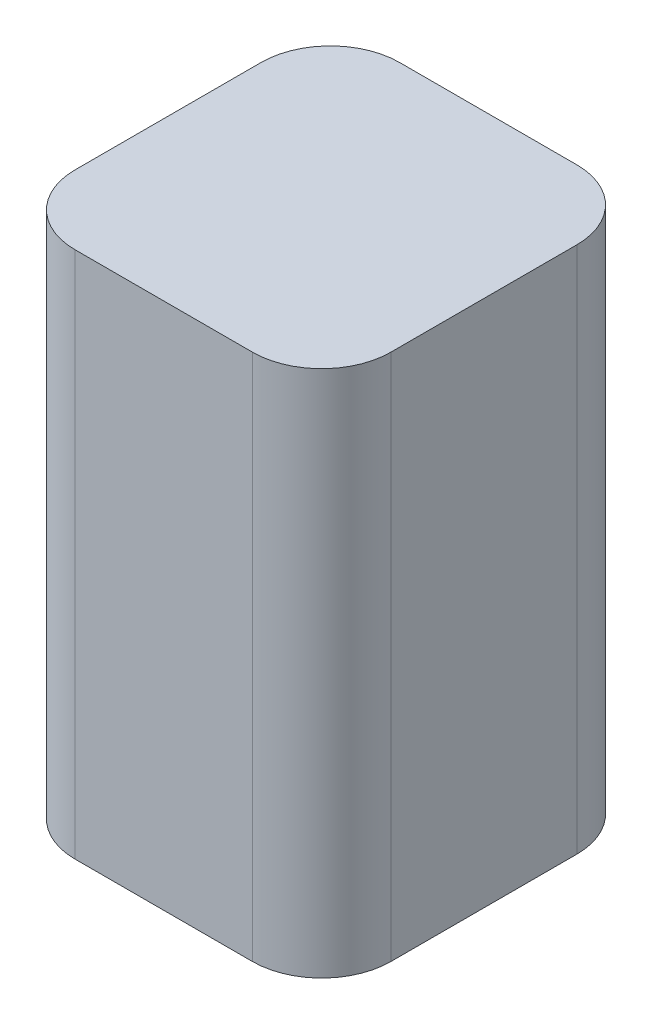
SolidWorks part; units mm, degrees
material "1060 Alloy"
ref_plane "Front Plane" through (0, 0, 0) normal (0, 0, 1) x (1, 0, 0)
ref_plane "Top Plane" through (0, 0, 0) normal (0, 1, 0) x (1, 0, 0)
ref_plane "Right Plane" through (0, 0, 0) normal (1, 0, 0) x (0, 0, -1)
sketch "Sketch1" plane through (0, 0, 0) normal (0, 0, 1) x (1, 0, 0)
  line L1 (-4.6355, 7.747) -> (4.6355, 7.747)
  line L2 (-4.6355, 7.747) -> (-4.6355, -7.747)
  line L3 (-4.6355, -7.747) -> (4.6355, -7.747)
  line L4 (4.6355, 7.747) -> (4.6355, -7.747)
  line L5 (-4.6355, 7.747) -> (4.6355, -7.747) construction
  line L6 (-4.6355, -7.747) -> (4.6355, 7.747) construction
  point P0 (0, 0)
  dimension "D1" = 9.271
  dimension "D2" = 15.494
extrude "Boss-Extrude1" add sketch "Sketch1" against normal blind 9.525
hole_wizard "1/4 (0.25) Diameter Hole1" positions "Sketch3" profile "Sketch2" hole size "1/4" standard "Ansi Inch"
sketch "Sketch3" plane through (0, 0, -9.525) normal (0, 0, -1) x (-1, 0, 0)
  point P0 (0, 0)
sketch "Sketch2" plane through (0, 0, -9.525) normal (1, 0, 0) x (0, 1, 0)
  line L0 (0, 0) -> (0, 8.2577)
  line L1 (0, 8.2577) -> (3.175, 6.35)
  line L2 (3.175, 6.35) -> (3.175, 0)
  line L5 (3.175, 0) -> (0, 0)
  line L10 (0, 8.2577) -> (-3.175, 6.35) construction
  line L11 (0, -6.35) -> (0, 107.95) construction
  dimension "Hole Dia." = 6.35
  dimension "Hole Depth" = 6.35
  dimension "Drill Angle" = 118
fillet "Fillet1" radius 2.032 4 edges at (-4.6355, 0, 0) (4.6355, 0, 0) (-4.6355, 0, -9.525) (4.6355, 0, -9.525)
